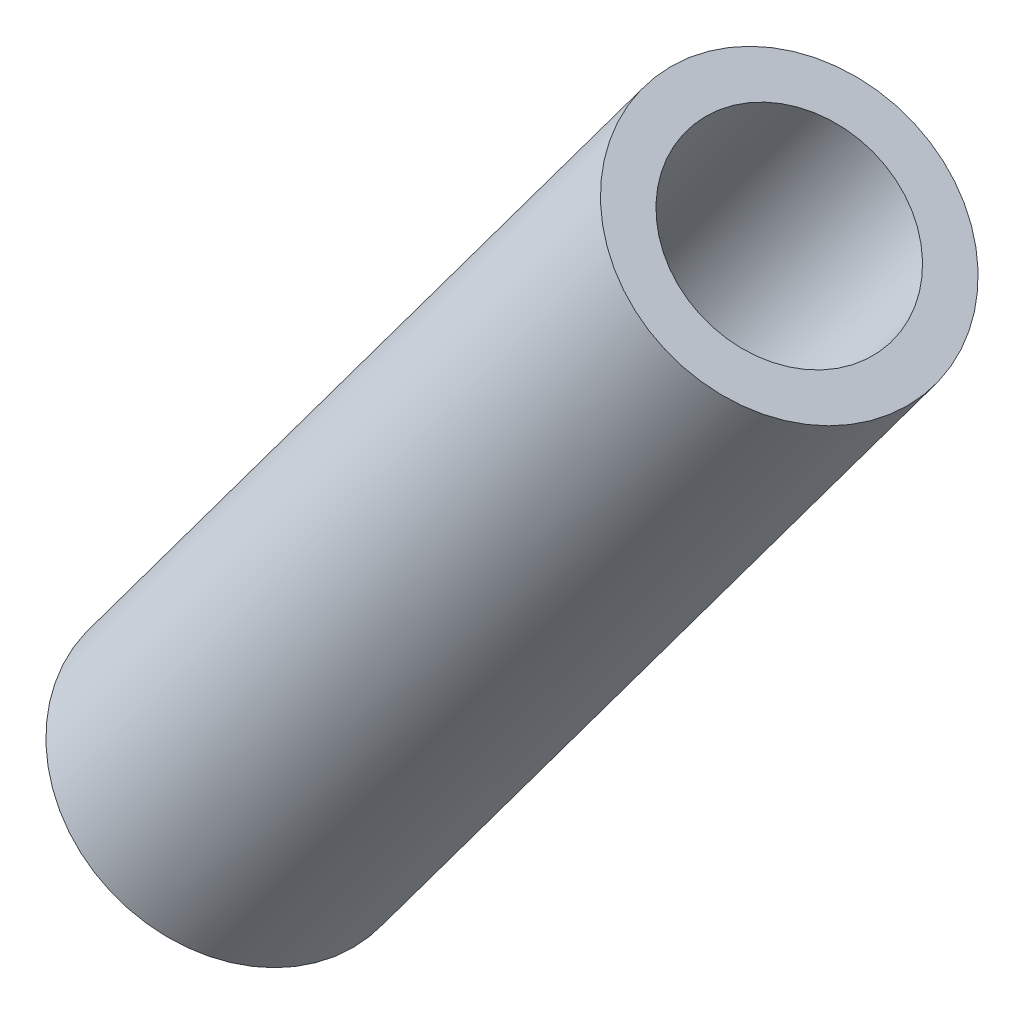
SolidWorks part; units mm, degrees
material "Silicon Rubber"
ref_plane "X-Y Datum" through (0, 0, 0) normal (0, 0, 1) x (1, 0, 0)
ref_plane "X-Z Datum" through (0, 0, 0) normal (0, 1, 0) x (1, 0, 0)
ref_plane "Y-Z Datum" through (0, 0, 0) normal (1, 0, 0) x (0, 0, -1)
sketch3d "3DSketch1"
  line L0 (-20.5114, -27.616, 0) -> (30.2901, 40.7817, 0)
  circle A0 centre (-20.5114, -27.616, 0) radius 10 construction
  circle A1 centre (-20.5114, -27.616, 0) radius 10 construction
  circle A2 centre (30.2901, 40.7817, 0) radius 9.5 construction
  circle A3 centre (30.2901, 40.7817, 0) radius 9.5 construction
  point P5 (-14.5488, -19.5881, 0)
  point P7 (-14.5488, -19.5881, 0)
  point P11 (35.9546, 48.4082, 0)
  point P12 (35.9546, 48.4082, 0)
sweep "Sweep1" add path "3DSketch1" circular profile diameter 26.9875 parameters "D3"=26.9875
sweep "Cut-Sweep1" cut path "3DSketch1<2>" circular profile diameter 19.05 parameters "D3"=19.05
sketch3d "3DSketch1<2>" same geometry as "3DSketch1"
sketch3d "3DSketch2"
  line L0 (-20.5114, -27.616, 0) -> (30.2901, 40.7817, 0) construction
  circle A1 centre (4.8894, 6.5829, 0) radius 9.525 construction
  circle A4 centre (30.2901, 40.7817, 0) radius 9.525 construction
  point P4 (-0.79, -1.0637, 0)
  point P8 (24.6107, 33.1351, 0)
